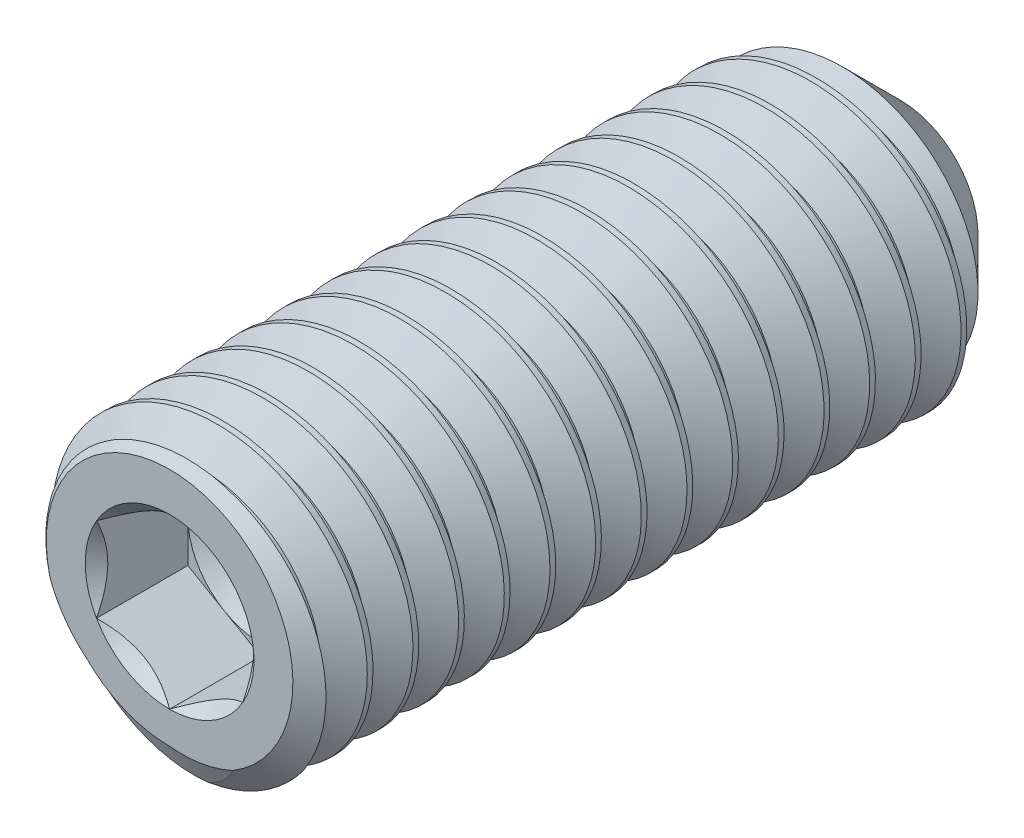
SolidWorks part; units mm, degrees
other "Imported1" parameters "D3"=22, "D1"=46.842, "Length"=20, "Drive Size"=4, "Thread Size"=8, "Thread Pitch"=1.25, "hex Depth"=2.5, "D2"=0.9112, "Dia"=12, "D4"=2.3829, "Cup Point Dia"=3.3528, "D5"=1.436, "D6"=1.4986, "D7"=5.0014, "Pitch"=1.75
ref_plane "Front" through (0, 0, 0) normal (0, 0, 1) x (1, 0, 0)
ref_plane "Top" through (0, 0, 0) normal (0, 1, 0) x (1, 0, 0)
ref_plane "Right" through (0, 0, 0) normal (1, 0, 0) x (0, 0, -1)
sketch "Sketch1" plane through (0, 0, 0) normal (1, 0, 0) x (0, 0, -1)
  line L0 (10, 4) -> (-10, 4) construction
  line L1 (-10, 4) -> (-10, -4) construction
  line L2 (-10, -4) -> (10, -4) construction
  line L3 (10, -4) -> (10, 4) construction
  line L4 (-10, 2) -> (-10, -2) construction
  line L5 (9.9219, 4.1353) -> (11.1719, 4.1353) construction
  line L6 (11.1719, 4.1353) -> (10.5469, 3.0528) construction
  line L7 (10.5469, 3.0528) -> (9.9219, 4.1353) construction
  line L8 (9.9609, 4.0677) -> (11.1328, 4.0677) construction
  line L9 (10, 4) -> (11.0938, 4) construction
  line L10 (10.5469, 4.1353) -> (10.5469, 4) construction
  line L11 (10.4688, 3.1881) -> (10.625, 3.1881) construction
  line L12 (10.5469, 3.1881) -> (10.5469, 3.0528) construction
  point P3 (0, 4)
  point P19 (10.5469, 4.0677)
  point P24 (-10, 0)
  point P25 (-10, 0)
  dimension "D1" = 0.1562
sketch "Sketch11" plane through (0, 0, 0) normal (1, 0, 0) x (0, 0, -1)
  line L0 (-10, 0) -> (-10, 3.375)
  line L1 (-10, 3.375) -> (-9.5624, 4)
  line L2 (-9.5624, 4) -> (8.125, 4)
  line L3 (8.125, 4) -> (10, 2.125)
  line L4 (10, 2.125) -> (8.7232, 0)
  line L5 (8.7232, 0) -> (-10, 0)
  line L6 (8.7232, 0) -> (10, 0) construction
  line L7 (10, 0) -> (10, 2.125) construction
  line L8 (10, -2.125) -> (8.7232, 0) construction
  line L9 (-9.5624, -4) -> (8.125, -4) construction
  line L10 (-10, -4) -> (10, -4) construction
  line L11 (-10, 4) -> (-10, -4) construction
  line L12 (10, -4) -> (10, 4) construction
  point P11 (5.625, -4)
  point P12 (-10, 4)
  dimension "D3" = 35
  dimension "D5" = 118
  dimension "D6" = 45
  dimension "D1" = 0.625
  dimension "D2" = 4.375
  dimension "D4" = 1.875
revolve "Revolve1" add sketch "Sketch11" angle 360 about L6
sketch "Sketch2" plane through (0, 0, 10) normal (0, 0, 1) x (1, 0, 0)
  line L1 (0, 2.3094) -> (-2, 1.1547)
  line L2 (-2, 1.1547) -> (-2, -1.1547)
  line L3 (-2, -1.1547) -> (0, -2.3094)
  line L4 (0, -2.3094) -> (2, -1.1547)
  line L5 (2, -1.1547) -> (2, 1.1547)
  line L6 (2, 1.1547) -> (0, 2.3094)
  circle A0 centre (0, 0) radius 2 construction
  circle A1 centre (0, 0) radius 4 construction
extrude "Cut-Extrude1" cut sketch "Sketch2" against normal blind 2.5
sketch "Sketch3" plane through (0, 0, 10) normal (0, 0, 1) x (1, 0, 0)
  circle A0 centre (0, 0) radius 2.3094
extrude "Cut-Extrude2" cut sketch "Sketch3" against normal through all draft 45
sketch "Sketch4" plane through (0, 0, 7.5) normal (0, 0, 1) x (1, 0, 0)
  circle A0 centre (0, 0) radius 2 construction
  circle A1 centre (0, 0) radius 2
extrude "Cut-Extrude3" cut sketch "Sketch4" against normal through all draft 60
sketch "Sketch13" plane through (0, 0, 0) normal (1, 0, 0) x (0, 0, -1)
  line L0 (0, -4) -> (0, 4) construction
  line L2 (-9.5624, 4) -> (8.125, 4) construction
  line L4 (8.7232, 0) -> (-10, 0) construction
  point P0 (0.7232, 0)
  point P4 (0, 0)
  point P9 (-0.7232, 0)
  dimension "D1" = 8
ref_plane "Plane1" through (0, 0, -10) normal (0, 0, 1) x (1, 0, 0)
sketch "Sketch5" plane through (0, 0, -10) normal (0, 0, 1) x (1, 0, 0)
  circle A0 centre (0, 0) radius 4 construction
  circle A1 centre (0, 0) radius 4
curve "Helix/Spiral1" pitch 1.25 height 22 radius 4 centre (0, 0, -10) axis (0, 0, 1) start towards (0, 1, 0)
sketch "Sketch6" plane through (0, 0, 0) normal (1, 0, 0) x (0, 0, -1)
  line L0 (9.9219, 4.1353) -> (11.1719, 4.1353) construction
  line L1 (11.1719, 4.1353) -> (10.5469, 3.0528) construction
  line L2 (10.5469, 3.0528) -> (9.9219, 4.1353) construction
  line L3 (10.5469, 4.1353) -> (10.5469, 4) construction
  line L4 (10, 4) -> (11.0938, 4) construction
  line L5 (10.5469, 3.1881) -> (10.5469, 3.0528) construction
  line L6 (10.4688, 3.1881) -> (9.9609, 4.0677)
  line L7 (9.9609, 4.0677) -> (11.1328, 4.0677)
  line L8 (9.9609, 4.0677) -> (11.1328, 4.0677) construction
  line L10 (10.4688, 3.1881) -> (10.625, 3.1881) construction
  line L12 (10.625, 3.1881) -> (10.4688, 3.1881)
  line L13 (11.1328, 4.0677) -> (10.625, 3.1881)
  point P9 (10.5469, 4)
  point P14 (10.5469, 4.0677)
  point P15 (10.5469, 4.0677)
  point P16 (10.5469, 3.1881)
  dimension "D1" = 1.25
  dimension "D2" = 0.1562
sweep "Cut-Sweep1" cut profiles "Sketch6" path "Helix/Spiral1"
equation "\"D3@Helix/Spiral1\" = \"Length@Sketch1\" * 1.1"
equation "\"hex Depth@Cut-Extrude1\" = \"Drive Size@Sketch1\" * .625"
equation "\"D1@Sketch6\" = \"Thread Pitch@Sketch1\""
equation "\"D2@Sketch6\" = \"D1@Sketch6\" / 8"
equation "\"D1@Sketch11\" = \"Thread Pitch@Sketch1\" * .5"
equation "\"D2@Sketch11\" = \"Thread Pitch@Sketch1\" * 3.5"
equation "\"D1@Helix/Spiral1\" = \"Thread Pitch@Sketch1\""
equation "\"D4@Sketch11\" = \"Thread Pitch@Sketch1\" * 1.5"
equation "\"D1@Sketch1\" = \"Thread Pitch@Sketch1\" / 8"
equation "\"D1@Sketch13\"=\"Thread Size@Sketch1\""
